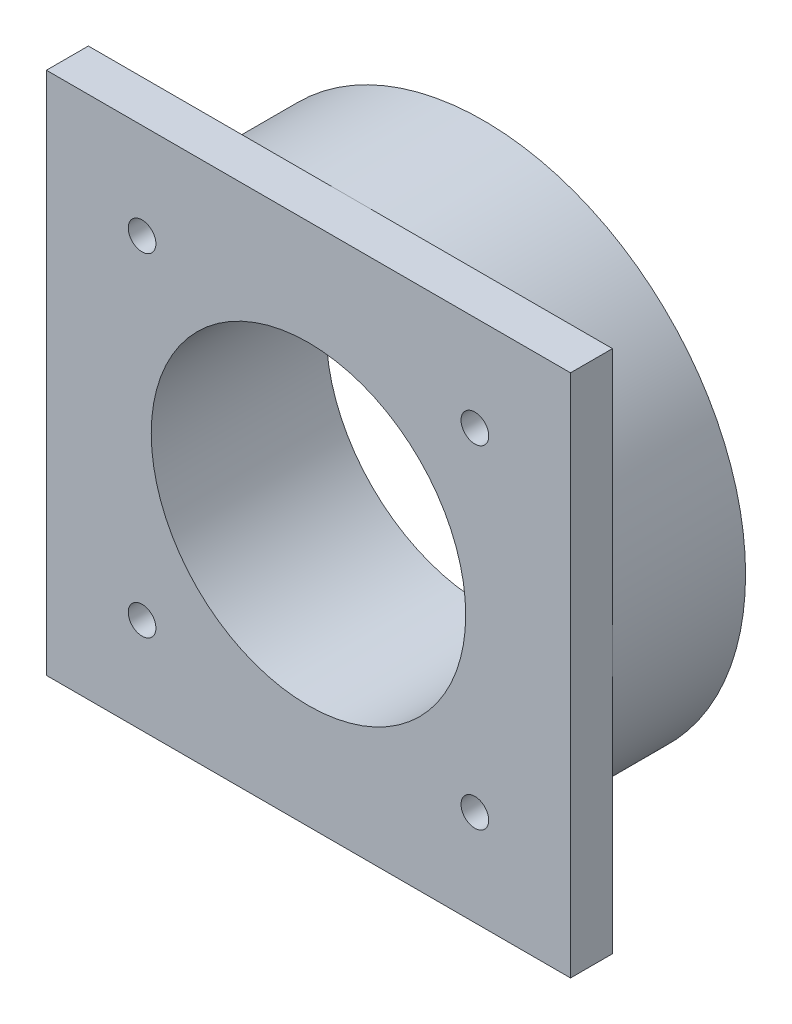
SolidWorks part; units mm, degrees
ref_plane "Front Plane" through (0, 0, 0) normal (0, 0, 1) x (1, 0, 0)
ref_plane "Top Plane" through (0, 0, 0) normal (0, 1, 0) x (1, 0, 0)
ref_plane "Right Plane" through (0, 0, 0) normal (1, 0, 0) x (0, 0, -1)
sketch "Sketch1" plane through (0, 0, 0) normal (0, 0, 1) x (1, 0, 0)
  circle A0 centre (0, 0) radius 25
  dimension "D1" = 50
extrude "Boss-Extrude1" add sketch "Sketch1" along normal blind 12.7
sketch "Sketch2" plane through (0, 0, 12.7) normal (0, 0, 1) x (1, 0, 0)
  line L0 (-25, -25) -> (25, 25) construction
  line L1 (-25, 25) -> (25, 25)
  line L2 (-25, 25) -> (-25, -25)
  line L3 (-25, -25) -> (25, -25)
  line L4 (25, 25) -> (25, -25)
  line L5 (-25, 25) -> (25, -25) construction
  line L6 (0, 0) -> (0, 16.6497) construction
  dimension "D1" = 50
  dimension "D2" = 50
extrude "Boss-Extrude2" add sketch "Sketch2" along normal blind 4
sketch "Sketch3" plane through (0, 0, 16.7) normal (0, 0, 1) x (1, 0, 0)
  line L1 (-15.875, 15.875) -> (15.875, 15.875) construction
  line L2 (15.875, 15.875) -> (15.875, -15.875) construction
  line L3 (15.875, -15.875) -> (-15.875, -15.875) construction
  line L4 (-15.875, -15.875) -> (-15.875, 15.875) construction
  line L5 (-15.875, 15.875) -> (15.875, -15.875) construction
  line L6 (0, 0) -> (-3.1518, -3.1518) construction
  circle A0 centre (-15.875, 15.875) radius 1.32
  circle A1 centre (15.875, 15.875) radius 1.32
  circle A2 centre (15.875, -15.875) radius 1.32
  circle A3 centre (-15.875, -15.875) radius 1.32
  dimension "D1" = 2.64
  dimension "D4" = 31.75
  dimension "D5" = 31.75
  dimension "D2" = 2
  dimension "D3" = 2
extrude "Cut-Extrude1" cut sketch "Sketch3" against normal through all
sketch "Sketch4" plane through (0, 0, 16.7) normal (0, 0, 1) x (1, 0, 0)
  circle A0 centre (0, 0) radius 15
  dimension "D1" = 30
extrude "Cut-Extrude2" cut sketch "Sketch4" against normal through all
